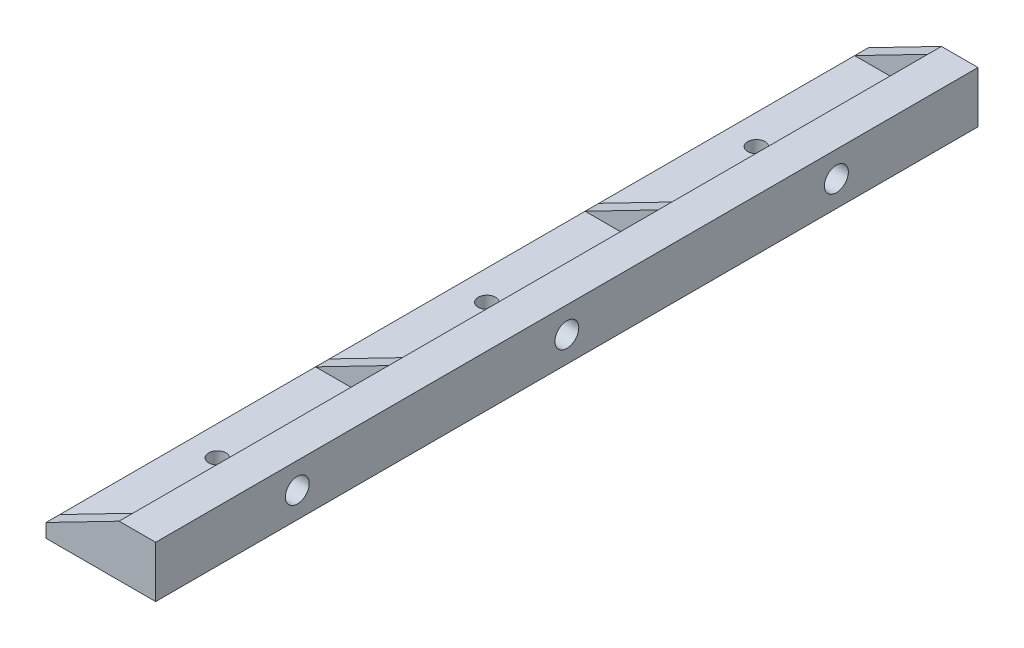
SolidWorks part; units mm, degrees
ref_plane "Front Plane" through (0, 0, 0) normal (0, 0, 1) x (1, 0, 0)
ref_plane "Top Plane" through (0, 0, 0) normal (0, 1, 0) x (1, 0, 0)
ref_plane "Right Plane" through (0, 0, 0) normal (1, 0, 0) x (0, 0, -1)
sketch "Sketch1" plane through (0, 0, 0) normal (0, 0, 1) x (1, 0, 0)
  line L0 (0, 0) -> (0, 11.25)
  line L1 (0, 11.25) -> (-8, 11.25)
  line L2 (-8, 11.25) -> (-8, 6)
  line L3 (-11, 3) -> (-24, 3)
  line L4 (-24, 3) -> (-24, 0)
  line L6 (-24, 0) -> (0, 0)
  arc A0 (-8, 6) -> (-11, 3) centre (-11, 6) cw
  dimension "D1" = 3
  dimension "D2" = 11.25
  dimension "D3" = 24
  dimension "D4" = 8
  dimension "D5" = 3
extrude "Boss-Extrude1" add sketch "Sketch1" along normal blind 180
ref_plane "Plane2" through (0, 0, 0) normal (0, 0, -1) x (-1, 0, 0)
ref_plane "Plane4" through (0, 0, 90) normal (0, 0, -1) x (-1, 0, 0)
ref_plane "Plane5" through (0, 0, 60.5) normal (0, 0, -1) x (-1, 0, 0)
sketch "Sketch4" plane through (0, 0, 60.5) normal (0, 0, -1) x (-1, 0, 0)
  line L0 (8, 11.25) -> (24, 3)
sketch "Sketch5" plane through (0, 0, 0) normal (0, 0, -1) x (-1, 0, 0)
  line L0 (8, 11.25) -> (24, 3)
rib "Rib3" sketch "Sketch4" sketch "Sketch4" thickness 3 extrusion direction parallel to sketch draft on no parameters "D1"=3
rib "Rib4" sketch "Sketch5" sketch "Sketch5" thickness 3 extrusion direction parallel to sketch draft on no parameters "D1"=3
mirror "Mirror1" about plane through (0, 0, 90) normal (0, 0, -1) of "Rib3", "Rib4"
sketch "Sketch6" plane through (0, 0, 0) normal (1, 0, 0) x (0, 0, -1)
  line L0 (-180, 5.625) -> (0, 5.625) construction
  line L1 (-180, 0) -> (-180, 11.25) construction
  line L2 (0, 0) -> (0, 11.25) construction
  circle A0 centre (-149, 5.625) radius 2.3495
  circle A1 centre (-31, 5.625) radius 2.3495
  circle A2 centre (-90, 5.625) radius 2.3495
  point P6 (-149, 5.625)
  point P7 (-31, 5.625)
  point P8 (-90, 5.625)
  dimension "D3" = 4.699
  dimension "D1" = 31
  dimension "D2" = 31
sketch "Sketch9" plane through (0, 0, 0) normal (0, -1, 0) x (1, 0, 0)
  line L0 (-17.5, 180) -> (-17.5, 0) construction
  line L1 (-24, 180) -> (0, 180) construction
  line L2 (-24, 0) -> (0, 0) construction
  line L3 (-24, 180) -> (-24, 0) construction
  point P6 (-17.5, 149)
  point P7 (-17.5, 31)
  point P10 (-17.5, 90)
  dimension "D1" = 31
  dimension "D2" = 31
  dimension "D3" = 6.5
hole_wizard "#6 Clearance Hole1" positions "Sketch10" profile "Sketch11" hole size "#6" standard "ANSI Inch" end condition through all
sketch "Sketch10" plane through (0, 0, 0) normal (0, -1, 0) x (-1, 0, 0)
  point P0 (17.5, -31)
  point P3 (17.5, -149)
  point P6 (17.5, -90)
sketch "Sketch11" plane through (-17.5, 0, 31) normal (1, 0, 0) x (0, 0, -1)
  line L0 (0, 0) -> (0, 11.25)
  line L1 (0, 11.25) -> (1.8986, 11.25)
  line L2 (1.8986, 11.25) -> (1.8986, 0)
  line L5 (1.8986, 0) -> (0, 0)
  line L11 (0, -6.35) -> (0, 107.95) construction
  dimension "Thru Hole Dia." = 3.7973
  dimension "Thru Hole Depth" = 11.25
extrude "Cut-Extrude1" cut sketch "Sketch6" against normal offset from surface (7 mm away) 1 up to face at (-8, 8.625, 149)
sketch "Sketch12" plane through (0, 0, 0) normal (1, 0, 0) x (0, 0, -1)
  circle A0 centre (-149, 5.625) radius 2.6162
  circle A1 centre (-31, 5.625) radius 2.6162
  circle A2 centre (-90, 5.625) radius 2.6162
  dimension "D1" = 5.2324
extrude "Cut-Extrude2" cut sketch "Sketch12" against normal blind 6.35
